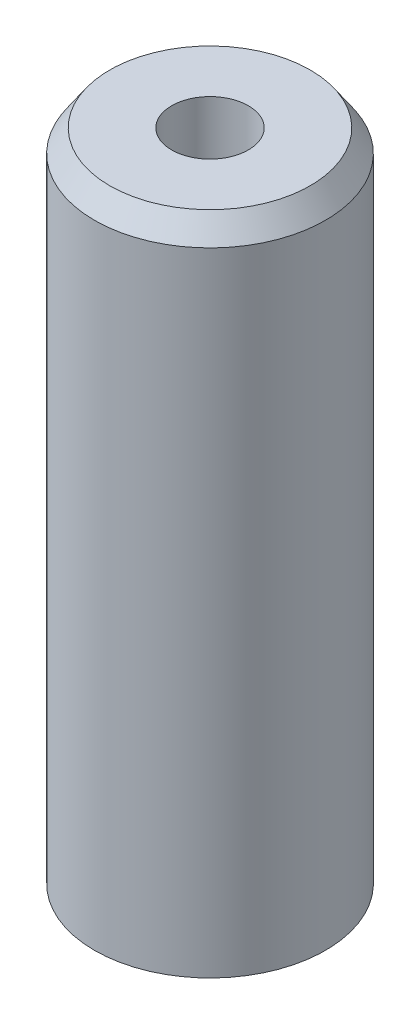
SolidWorks part; units mm, degrees
ref_plane "Front Plane" through (0, 0, 0) normal (0, 0, 1) x (1, 0, 0)
ref_plane "Top Plane" through (0, 0, 0) normal (0, 1, 0) x (1, 0, 0)
ref_plane "Right Plane" through (0, 0, 0) normal (1, 0, 0) x (0, 0, -1)
sketch "Sketch1" plane through (0, 0, 0) normal (0, 1, 0) x (1, 0, 0)
  circle A0 centre (0, 0) radius 27.5
  dimension "SHAFT_OD" = 55
extrude "Boss-Extrude1" add sketch "Sketch1" along normal blind 159.4417
sketch "Sketch2" plane through (0, 0, 0) normal (0, 1, 0) x (1, 0, 0)
  circle A0 centre (0, 0) radius 9.127
  dimension "BORE_D" = 18.2539
extrude "Cut-Extrude1" cut sketch "Sketch2" along normal through all
chamfer "Chamfer1" distance 5.3092 angle 34.364 2 edges at (0, 159.4417, 27.5) (0, 0, 27.5) first distance on face at (0, 159.4417, 27.5) first distance on face at (0, 0, 9.127)
